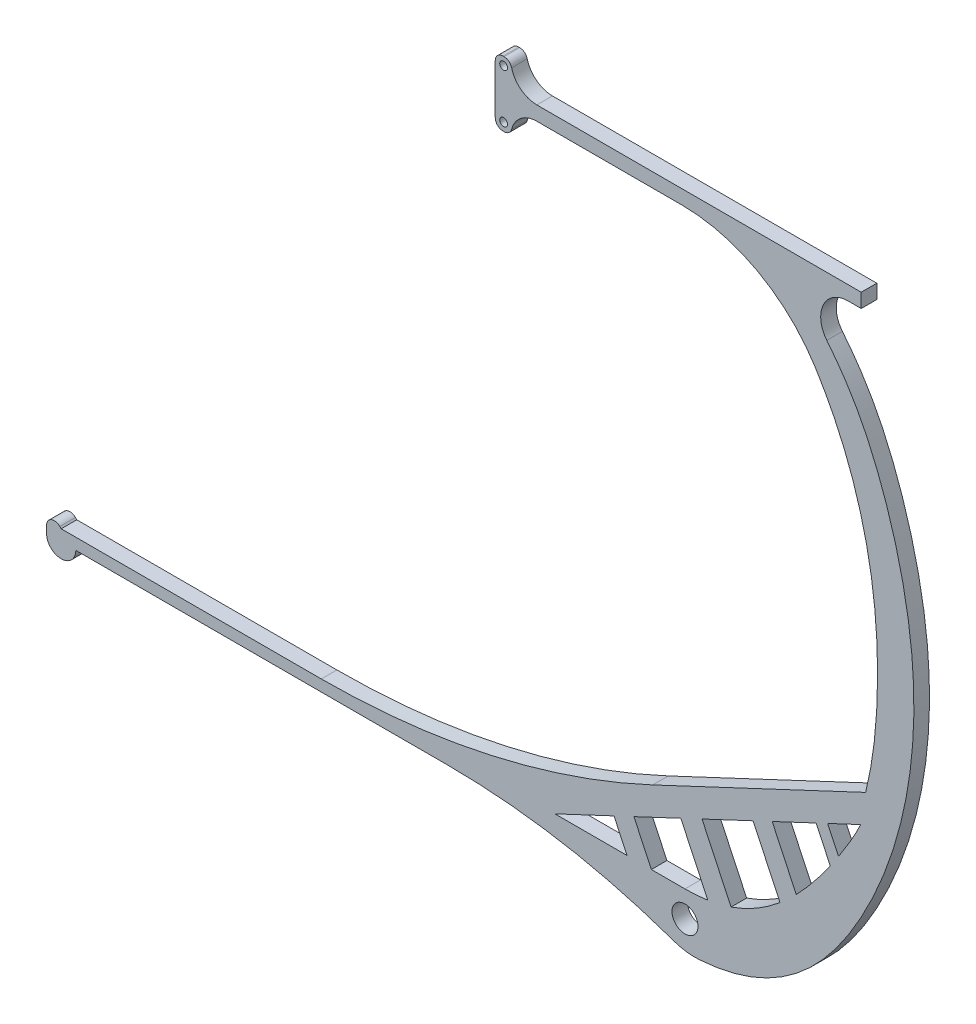
SolidWorks part; units mm, degrees
ref_plane "Front Plane" through (0, 0, 0) normal (0, 0, 1) x (1, 0, 0)
ref_plane "Top Plane" through (0, 0, 0) normal (0, 1, 0) x (1, 0, 0)
ref_plane "Right Plane" through (0, 0, 0) normal (1, 0, 0) x (0, 0, -1)
sketch "Sketch1" plane through (0, 0, 0) normal (0, 0, 1) x (1, 0, 0)
  line L0 (0, 0) -> (0, 240) construction
  line L1 (0, 0) -> (-240, 0) construction
  line L2 (-240, 10) -> (-139.9277, 10)
  line L3 (-73, 252.5) -> (-67, 227.5) construction
  line L4 (-73, 252.5) -> (-67, 252.5)
  line L5 (-73, 252.5) -> (-73, 227.5)
  line L6 (-73, 227.5) -> (-67, 227.5)
  line L7 (-67, 252.5) -> (-67, 242.7232)
  line L8 (-67, 242.7232) -> (67.8023, 242.7232)
  line L9 (67.8023, 242.7232) -> (67.8023, 237.2768)
  line L10 (-70, 240) -> (67.8023, 240) construction
  line L11 (-67, 237.2768) -> (0, 237.2768)
  line L13 (-67, 237.2768) -> (-67, 227.5)
  line L14 (62.7768, 237.2768) -> (67.8023, 237.2768)
  line L15 (-240, 5.6259) -> (-91.671, 5.6259)
  line L16 (-5.4617, -9.0825) -> (-4.4036, -9.4544)
  line L17 (-240, 10) -> (-240, 5.6259)
  line L18 (-12.4185, 38.4463) -> (69.5009, 76.9119)
  line L19 (-50.0378, 10) -> (-27.3091, 20.6723)
  line L20 (-50.0378, 10) -> (-22.2979, 10)
  line L21 (-27.3091, 20.6723) -> (-22.2979, 10)
  line L22 (-19.6448, 24.2711) -> (-12.9438, 10)
  line L23 (-1.6026, 32.7429) -> (8.7763, 10.639)
  line L24 (6.5594, 36.5754) -> (17.7154, 12.8167)
  line L25 (26.1979, 45.7968) -> (36.5591, 23.7307)
  line L26 (33.5494, 49.2487) -> (42.8029, 29.5416)
  line L27 (50.4521, 57.1854) -> (55.8808, 45.624)
  line L28 (54.8837, 59.2663) -> (59.0749, 50.3403)
  line L29 (-19.6448, 24.2711) -> (-1.6026, 32.7429)
  line L30 (-12.9438, 10) -> (0, 10)
  line L31 (6.5594, 36.5754) -> (26.1979, 45.7968)
  line L32 (33.5494, 49.2487) -> (50.4521, 57.1854)
  line L33 (54.8837, 59.2663) -> (67.5904, 65.2328)
  circle A0 centre (0, 0) radius 5
  arc A1 (-91.671, 5.6259) -> (-5.4617, -9.0825) centre (-91.671, -254.3741) cw
  arc A2 (5.5987, -10.8122) -> (-4.4036, -9.4544) centre (3.8949, 14.1574) cw
  arc A3 (62.7768, 237.2768) -> (54.564, 220.0496) centre (62.7768, 226.7056) ccw
  arc A5 (50.0506, 208.9535) -> (-1.2317, 237.2768) centre (-1.2317, 176.6892) ccw
  arc A6 (-12.4185, 38.4463) -> (-139.9277, 10) centre (-139.9277, 310) cw
  spline S0 degree 3 poles (0, 10) (2.8989, 10) (5.8241, 10.1913) (8.7763, 10.639) knots 0 0 0 0 0.042649 0.042649 0.042649 0.042649
  spline S1 degree 3 poles (5.5987, -10.8122) (36.653, -8.6932) (78.2276, 36.4007) (94.5903, 116.4656) (76.6268, 184.7367) (63.3063, 209.2625) (54.564, 220.0496) knots 0.015792 0.015792 0.015792 0.015792 0.284946 0.6284 0.811917 0.936974 0.936974 0.936974 0.936974
  spline S2 degree 3 poles (69.5009, 76.9119) (72.2645, 87.9441) (76.5273, 125.0485) (70.2686, 171.942) (53.7372, 203.0939) (50.0506, 208.9535) knots 0.407524 0.407524 0.407524 0.407524 0.537195 0.818084 0.885363 0.885363 0.885363 0.885363
  spline S3 degree 3 poles (17.7154, 12.8167) (23.8768, 14.9183) (30.1555, 18.3696) (36.5591, 23.7307) knots 0.085298 0.085298 0.085298 0.085298 0.172679 0.172679 0.172679 0.172679
  spline S4 degree 3 poles (42.8029, 29.5416) (44.4942, 31.2768) (48.8777, 36.1178) (53.3198, 41.9704) (55.8808, 45.624) knots 0.200899 0.200899 0.200899 0.200899 0.223688 0.259664 0.259664 0.259664 0.259664
  spline S5 degree 3 poles (59.0749, 50.3403) (62.6324, 55.7796) (65.6686, 61.0821) (67.5904, 65.2328) knots 0.275096 0.275096 0.275096 0.275096 0.3286 0.3286 0.3286 0.3286
  point P4 (0, 240)
  point P5 (-240, 0)
  point P6 (0, 74.9)
  point P11 (-70, 240)
  point P16 (-70, 240)
  point P62 (0, 0)
  dimension "D1" = 10
  dimension "D2" = 260
  dimension "D8" = 25.0276
  dimension "D10" = 300
  dimension "D3" = 240
  dimension "D4" = 165.1
  dimension "D5" = 70
  dimension "D6" = 25
  dimension "D7" = 6
  dimension "D9" = 10
extrude "Boss-Extrude1" add sketch "Sketch1" along normal blind 3 and the other way blind 3 contours A2 S1 A3 L14 L9 L8 L7 L4 L5 L6 L13 L11 A5 S0 L2 L17 L15 A1 L16 A0 region at (-189.9638, 5.7929, 0)
fillet "Fillet1" radius 10 2 edges at (-67, 242.7232, 0) (-67, 237.2768, 0)
sketch "Sketch3" plane through (0, 0, 3) normal (0, 0, 1) x (1, 0, 0)
  line L0 (-73, 240) -> (-57.889, 240) construction
  line L3 (-73, 252.5) -> (-73, 227.5) construction
  line L4 (-69.7846, 249.3969) -> (-69.7846, 230.6031) construction
  circle A0 centre (-69.7846, 249.3969) radius 1.5
  circle A1 centre (-69.7846, 230.6031) radius 1.5
  point P8 (-69.7846, 240)
  dimension "D1" = 3
extrude "Cut-Extrude1" cut sketch "Sketch3" against normal through all
fillet "Fillet2" radius 3 4 edges at (-67, 227.5, 0) (-73, 227.5, 0) (-67, 252.5, 0) (-73, 252.5, 0)
sketch "Sketch4" plane through (0, 0, 3) normal (0, 0, 1) x (1, 0, 0)
  line L1 (-245.6259, 5.6259) -> (-245.6259, 8.3833)
  line L2 (-240, 5.6259) -> (-234.3741, 5.6259)
  line L4 (-240, 10) -> (-240, 6.943)
  line L5 (-240, 10) -> (-240, 5.6259) construction
  line L6 (-240, 6.943) -> (-240, 5.6259)
  line L7 (-240.5046, 10.5046) -> (-240, 10)
  arc A0 (-245.6259, 5.6259) -> (-234.3741, 5.6259) centre (-240, 5.6259) ccw
  arc A2 (-245.6259, 8.3833) -> (-240.5046, 10.5046) centre (-242.6259, 8.3833) cw
  dimension "D1" = 3
extrude "Boss-Extrude2" add sketch "Sketch4" against normal up to surface (6 mm away) up to face at (-68.2846, 249.3969, -3)
